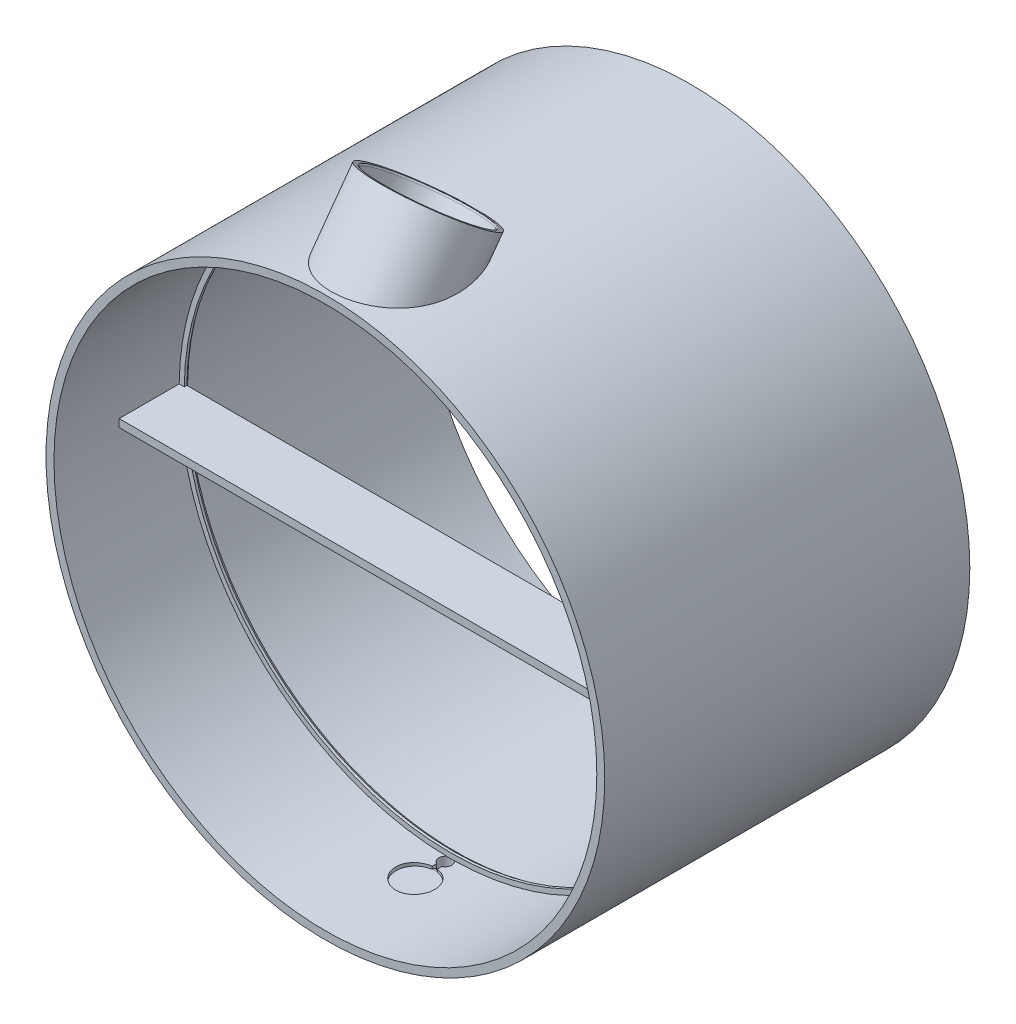
SolidWorks part; units mm, degrees
ref_plane "Front Plane" through (0, 0, 0) normal (0, 0, 1) x (1, 0, 0)
ref_plane "Top Plane" through (0, 0, 0) normal (0, 1, 0) x (1, 0, 0)
ref_plane "Right Plane" through (0, 0, 0) normal (1, 0, 0) x (0, 0, -1)
sketch "Sketch2" plane through (0, 0, 0) normal (0, 0, 1) x (1, 0, 0)
  circle A0 centre (0, 0) radius 107.15
  dimension "D1" = 214.3
extrude "Boss-Extrude2" add sketch "Sketch2" along normal blind 70 and the other way blind 70
sketch "Sketch3" plane through (0, 0, 70) normal (0, 0, 1) x (1, 0, 0)
  circle A0 centre (0, 0) radius 105.65
  dimension "D1" = 211.3
ref_plane "Plane2" through (0, 0, 45) normal (0, 0, 1) x (1, 0, 0)
ref_plane "Plane3" through (0, 107.15, 0) normal (0, 1, 0) x (1, 0, 0)
sketch "Sketch8" plane through (0, 107.15, 0) normal (0, 1, 0) x (1, 0, 0)
  line L0 (0, 70) -> (0, -40)
  line L1 (107.15, 70) -> (-107.15, 70) construction
  line L2 (0, -181.6691) -> (0, 181.6691) construction
  dimension "D1" = 110
ref_plane "Plane4" through (0, 107.15, 40) normal (0, 0, 1) x (1, 0, 0)
ref_axis "Axis1" through (60.5, 107.15, 40) along (-1, 0, 0)
ref_plane "Plane5" through (0, 51.1095, -37.1332) normal (0, -0.809, 0.5878) x (1, 0, 0)
sketch "Sketch10" plane through (0, 51.1095, -37.1332) normal (0, -0.809, 0.5878) x (1, 0, 0)
  circle A0 centre (0, 95.3419) radius 19
  dimension "D1" = 38
extrude "Cut-Extrude2" cut sketch "Sketch10" along normal mid plane 20
ref_plane "Plane6" through (0, 63.2447, -45.95) normal (0, -0.809, 0.5878) x (1, 0, 0)
ref_axis "Axis2" through (0, 49.8364, 81.6408) along (0, 0.809, -0.5878)
sketch "Sketch16" plane through (0, 63.2447, -45.95) normal (0, -0.809, 0.5878) x (1, 0, 0)
  circle A0 centre (0, 95.3419) radius 20
  dimension "D1" = 40
sketch "Sketch18" plane through (0, 63.2447, -45.95) normal (0, -0.809, 0.5878) x (1, 0, 0)
  line L0 (0, -181.6691) -> (0, 181.6691) construction
  circle A0 centre (0, 95.3419) radius 22.5
  dimension "D1" = 45
extrude "Boss-Extrude6" add sketch "Sketch18" along normal blind 32 and the other way blind 1
sketch "Sketch22" plane through (0, 63.2447, -45.95) normal (0, -0.809, 0.5878) x (1, 0, 0)
  line L0 (0, -181.6691) -> (0, 181.6691) construction
  circle A0 centre (0, 95.3419) radius 19
  dimension "D1" = 38
sketch "Sketch26" plane through (0, 51.1095, -37.1332) normal (0, -0.809, 0.5878) x (1, 0, 0)
  circle A0 centre (0, 95.3419) radius 19
ref_axis "Axis3" through (0, 117.4734, 32.4996) along (0, -0.809, 0.5878)
ref_plane "Plane7" through (0, 0, 0) normal (-1, 0, 0) x (0, 0, 1)
sketch "Sketch27" plane through (0, 0, 0) normal (-1, 0, 0) x (0, 0, 1)
  line L0 (40, 107.15) -> (276.5347, 1.838)
  line L1 (-70, 107.15) -> (40, 107.15) construction
  line L2 (40, 107.15) -> (63.2582, -114.1368)
  line L3 (78.2472, 54.5072) -> (-16.3702, 184.7369) construction
  dimension "D1" = 30
  dimension "D2" = 30
sketch "Sketch31" plane through (0, 0, 0) normal (-1, 0, 0) x (0, 0, 1)
  line L0 (40, 107.15) -> (205.9898, -4.8115)
  line L1 (40, 107.15) -> (93.2086, -78.4105)
  line L2 (78.2472, 54.5072) -> (-16.3702, 184.7369) construction
  dimension "D1" = 20
  dimension "D2" = 20
ref_plane "Plane8" through (0, -107.15, 0) normal (0, 1, 0) x (1, 0, 0)
ref_plane "Plane9" through (0, 0, 70) normal (0, 0, 1) x (1, 0, 0)
ref_plane "Plane10" through (0, 0, -70) normal (0, 0, -1) x (-1, 0, 0)
sketch "Sketch39" plane through (0, -107.15, 0) normal (0, 1, 0) x (1, 0, 0)
  line L0 (0, 70) -> (0, -24)
  line L1 (0, 115.5498) -> (0, -115.5498) construction
  line L2 (0, -78.2472) -> (0, 16.3702) construction
  dimension "D1" = 94
ref_plane "Plane12" through (0, 0, 35.5) normal (0, 0, 1) x (1, 0, 0)
ref_plane "Plane13" through (0, -105.15, 0) normal (0, 1, 0) x (1, 0, 0)
ref_axis "Axis5" through (0, 116.215, 35.5) along (0, -1, 0)
sketch "Sketch54" plane through (0, -107.15, 0) normal (0, 1, 0) x (1, 0, 0)
  line L0 (0, 70) -> (0, 1.5)
  dimension "D1" = 68.5
sketch "Sketch56" plane through (0, -107.15, 0) normal (0, 1, 0) x (1, 0, 0)
  line L0 (0, -181.6691) -> (0, 181.6691) construction
  circle A0 centre (0, 1.5) radius 30.95
  dimension "D1" = 61.9
extrude "Boss-Extrude7" add sketch "Sketch56" along normal blind 5 and the other way blind 6
sketch "Sketch20" plane through (0, 0, 70) normal (0, 0, 1) x (1, 0, 0)
  circle A0 centre (0, 0) radius 104.1
  dimension "D1" = 208.2
extrude "Cut-Extrude3" cut sketch "Sketch20" against normal blind 140
sketch "Sketch51" plane through (0, -107.15, 0) normal (0, 1, 0) x (1, 0, 0)
  circle A0 centre (0, -24) radius 2.5
  dimension "D1" = 5
extrude "Cut-Extrude14" cut sketch "Sketch51" against normal blind 55 and the other way blind 5
sketch "Sketch58" plane through (0, -105.15, 0) normal (0, 1, 0) x (1, 0, 0)
  line L0 (0, -24) -> (1, -24)
  line L1 (1, -24) -> (1, -34.1928)
  line L2 (1, -34.1928) -> (-1, -34.1928)
  line L3 (-1, -34.1928) -> (-1, -24)
  line L4 (-1, -24) -> (0, -24)
  dimension "D1" = 1
  dimension "D2" = 1
  dimension "D3" = 2
extrude "Cut-Extrude15" cut sketch "Sketch58" along normal blind 5
sketch "Sketch44" plane through (0, -105.15, 0) normal (0, 1, 0) x (1, 0, 0)
  line L0 (0, -181.6691) -> (0, 181.6691) construction
  circle A0 centre (0, -35.5) radius 7.5
  dimension "D1" = 15
extrude "Cut-Extrude10" cut sketch "Sketch44" along normal blind 10
fillet "Fillet3" radius 1.5 1 edges at (0, -105.15, 26.5)
ref_plane "Plane14" through (0, 0, 22) normal (0, 0, 1) x (1, 0, 0)
ref_axis "Axis6" through (0, 0, -70) along (0, 0, 1)
sketch "Sketch61" plane through (0, 0, 22) normal (0, 0, 1) x (1, 0, 0)
  circle A0 centre (0, 0) radius 104.15
  dimension "D1" = 208.3
extrude "Boss-Extrude8" add sketch "Sketch61" against normal blind 2
sketch "Sketch62" plane through (0, 0, 22) normal (0, 0, 1) x (1, 0, 0)
  circle A0 centre (0, 0) radius 102.15
  dimension "D1" = 204.3
extrude "Cut-Extrude16" cut sketch "Sketch62" against normal blind 10
chamfer "Chamfer7" distance 1 angle 35 1 edges at (102.15, 0, 20) first distance on face at (102.15, 0, 22)
sketch "Sketch5" plane through (0, 0, 45) normal (0, 0, 1) x (1, 0, 0)
  line L1 (-105.65, -1.5) -> (105.65, -1.5)
  line L2 (-105.65, -1.5) -> (-105.65, 1.5)
  line L3 (-105.65, 1.5) -> (105.65, 1.5)
  line L4 (105.65, -1.5) -> (105.65, 1.5)
  line L5 (-105.65, -1.5) -> (105.65, 1.5) construction
  line L6 (-105.65, 1.5) -> (105.65, -1.5) construction
  point P0 (0, 0)
  dimension "D1" = 211.3
  dimension "D2" = 3
extrude "Boss-Extrude3" add sketch "Sketch5" against normal blind 24
sketch "Sketch24" plane through (0, 63.2447, -45.95) normal (0, -0.809, 0.5878) x (1, 0, 0)
  line L0 (0, -181.6691) -> (0, 181.6691) construction
  circle A0 centre (0, 95.3419) radius 18.25
  dimension "D1" = 36.5
extrude "Cut-Extrude6" cut sketch "Sketch24" along normal blind 50
sketch "Sketch23" plane through (0, 63.2447, -45.95) normal (0, -0.809, 0.5878) x (1, 0, 0)
  line L1 (0, -181.6691) -> (0, 181.6691) construction
  circle A0 centre (0, 95.3419) radius 20.45
  dimension "D1" = 40.9
extrude "Cut-Extrude5" cut sketch "Sketch23" along normal blind 7 and the other way blind 5
ref_plane "Plane15" through (0, -167.15, 0) normal (0, 1, 0) x (1, 0, 0)
chamfer "Chamfer1" distance 0.5 angle 45 1 edges at (0, -113.15, 29.45)
fillet "Fillet4" radius 0.6 1 edges at (0, 108.0741, 14.051)
ref_axis "Axis7" through (0, 0, -119.9757) along (0, 0, 1)
ref_plane "Plane16" through (0, 0, 0) normal (0, -1, 0) x (-1, 0, 0)
sketch "Sketch63" plane through (0, -113.15, 0) normal (0, -1, 0) x (1, 0, 0)
  line L0 (0, 24) -> (0, 11)
  line L1 (0, -70) -> (0, 40) construction
  dimension "D1" = 13
sketch "Sketch64" plane through (0, -113.15, 0) normal (0, -1, 0) x (1, 0, 0)
  circle A0 centre (0, 11) radius 13
  dimension "D1" = 26
sketch "Sketch67" plane through (0, 57.5816, -41.8355) normal (0, 0.809, -0.5878) x (1, 0, 0)
  line L0 (-7.8729, -76.4681) -> (7.8729, -76.4681)
  line L1 (7.8729, -76.4681) -> (7.8729, -79.7497)
  line L2 (7.8729, -79.7497) -> (-7.8729, -79.4887)
  line L3 (-7.8729, -79.4887) -> (-7.8729, -76.4681)
extrude "Cut-Extrude19" cut sketch "Sketch67" against normal blind 4
